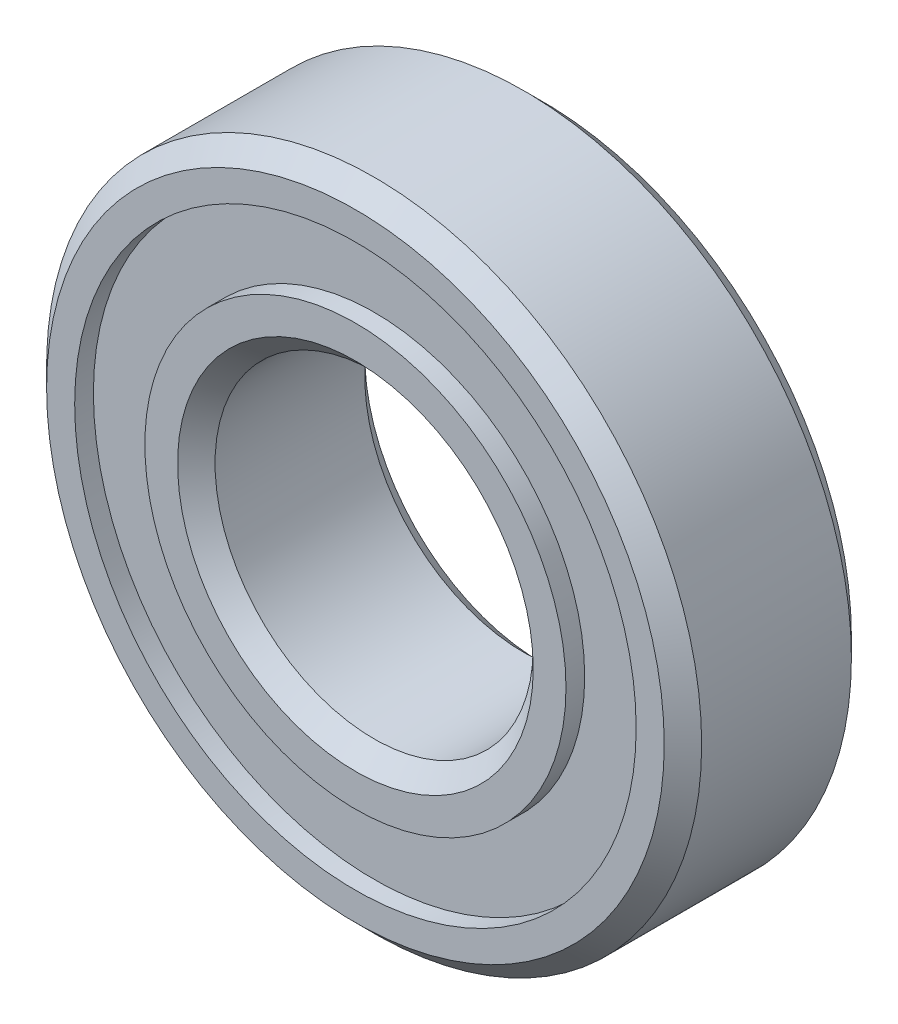
SolidWorks part; units mm, degrees
ref_plane "Front Plane" through (0, 0, 0) normal (0, 0, 1) x (1, 0, 0)
ref_plane "Top Plane" through (0, 0, 0) normal (0, 1, 0) x (1, 0, 0)
ref_plane "Right Plane" through (0, 0, 0) normal (1, 0, 0) x (0, 0, -1)
sketch "Sketch1" plane through (0, 0, 0) normal (0, 0, 1) x (1, 0, 0)
  circle A0 centre (0, 0) radius 17.5
  circle A1 centre (0, 0) radius 8.5
  dimension "D1" = 35
  dimension "D2" = 17
extrude "Boss-Extrude1" add sketch "Sketch1" along normal mid plane 10
sketch "Sketch2" plane through (0, 0, 5) normal (0, 0, 1) x (1, 0, 0)
  circle A0 centre (0, 0) radius 15
  circle A1 centre (0, 0) radius 11.25
  dimension "D1" = 22.5
  dimension "D2" = 30
extrude "Cut-Extrude1" cut sketch "Sketch2" against normal blind 1
mirror "Mirror1" about plane through (0, 0, 0) normal (0, 0, 1) of "Cut-Extrude1"
chamfer "Chamfer1" distance 1 angle 45 4 edges at (8.5, 0, -5) (8.5, 0, 5) (17.5, 0, -5) (17.5, 0, 5)
